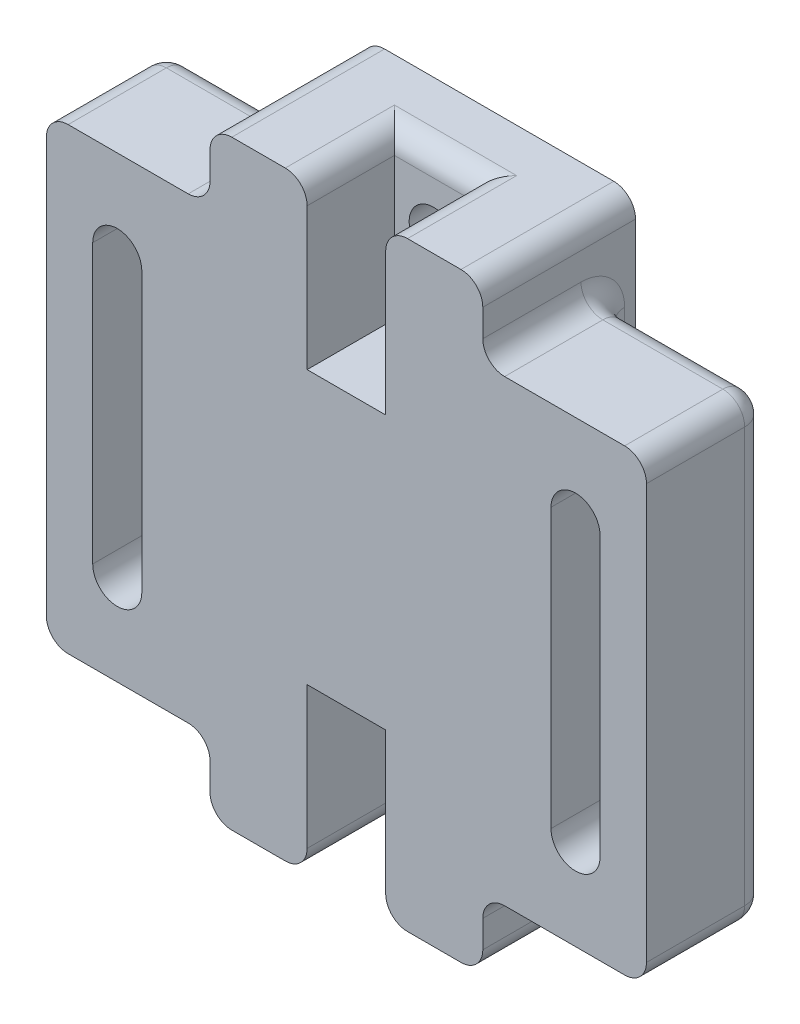
SolidWorks part; units mm, degrees
material "ABS"
ref_plane "Front Plane" through (0, 0, 0) normal (0, 0, 1) x (1, 0, 0)
ref_plane "Top Plane" through (0, 0, 0) normal (0, 1, 0) x (1, 0, 0)
ref_plane "Right Plane" through (0, 0, 0) normal (1, 0, 0) x (0, 0, -1)
sketch "Sketch1" plane through (0, 0, 0) normal (0, 1, 0) x (1, 0, 0)
  line L8 (0, 0) -> (15, 0)
  line L9 (15, 0) -> (15, 3)
  line L10 (15, 3) -> (40, 3)
  line L11 (40, 3) -> (40, 0)
  line L12 (40, 0) -> (55, 0)
  line L13 (55, 0) -> (55, -11)
  line L14 (55, -11) -> (0, -11)
  line L15 (0, -11) -> (0, 0)
  dimension "D1" = 55
  dimension "D2" = 14
  dimension "D3" = 11
  dimension "D4" = 25
extrude "Boss-Extrude1" add sketch "Sketch1" along normal blind 55
hole_wizard "M4 Clearance Hole1" positions "Sketch2" profile "Sketch3" hole size "M4" standard "ANSI Metric" end condition through all
sketch "Sketch2" plane through (0, 0, -3) normal (0, 0, -1) x (-1, 0, 0)
  line L0 (-27.5, 48.435) -> (-27.5, 6.565) construction
  line L4 (-40, 27.5) -> (-15, 27.5) construction
  line L5 (-40, 55) -> (-40, 0) construction
  line L6 (-15, 55) -> (-15, 0) construction
  point P0 (-27.5, 48.435)
  point P2 (-27.5, 6.565)
  point P27 (-27.5, 27.5)
  dimension "D1" = 41.87
sketch "Sketch3" plane through (27.5, 48.435, -3) normal (1, 0, 0) x (0, 1, 0)
  line L0 (0, 0) -> (0, 14)
  line L1 (0, 14) -> (2.25, 14)
  line L2 (2.25, 14) -> (2.25, 0)
  line L5 (2.25, 0) -> (0, 0)
  line L11 (0, -6.35) -> (0, 107.95) construction
  dimension "Thru Hole Dia." = 4.5
  dimension "Thru Hole Depth" = 14
hole_wizard "M4 Clearance Slot1" positions "Sketch4" profile "Sketch5" size "M4" standard "ANSI Metric" slot yes end condition through all
sketch "Sketch4" plane through (0, 0, 0) normal (0, 0, -1) x (-1, 0, 0)
  line L0 (-6.5, 42.5) -> (-6.5, 12.5) construction
  line L1 (0, 55) -> (0, 0) construction
  line L2 (-6.5, 27.5) -> (-48.5, 27.5) construction
  line L3 (-40, 55) -> (-15, 55) construction
  line L4 (-40, 55) -> (-15, 55) construction
  line L5 (-27.5, 55) -> (-27.5, 27.5) construction
  line L6 (-48.5, 27.5) -> (-55, 27.5) construction
  line L7 (-55, 55) -> (-55, 0) construction
  point P0 (-6.5, 27.5)
  point P4 (-48.5, 27.5)
  dimension "D1" = 30
  dimension "D3" = 42
sketch "Sketch5" plane through (6.5, 27.5, 0) normal (1, 0, 0) x (0, 1, 0)
  line L0 (0, 0) -> (0, 11)
  line L1 (0, 11) -> (2.25, 11)
  line L2 (2.25, 11) -> (2.25, 0)
  line L5 (2.25, 0) -> (0, 0)
  line L11 (0, -6.35) -> (0, 107.95) construction
  dimension "Thru Hole Dia." = 4.5
  dimension "Thru Hole Depth" = 11
sketch "Sketch6" plane through (0, 55, 0) normal (0, 1, 0) x (1, 0, 0)
  line L0 (0, -11) -> (55, -11) construction
  line L1 (23.9, -11) -> (31.1, -11)
  line L2 (23.9, -11) -> (23.9, -3)
  line L3 (23.9, -3) -> (31.1, -3)
  line L4 (31.1, -11) -> (31.1, -3)
  point P6 (27.5, -11)
  dimension "D1" = 7.2
  dimension "D2" = 8
extrude "Cut-Extrude1" cut sketch "Sketch6" against normal blind 15
ref_plane "Mirror Plane" through (0, 27.5, 0) normal (0, 1, 0) x (1, 0, 0)
mirror "Mirror1" about plane through (0, 27.5, 0) normal (0, 1, 0) of "Cut-Extrude1"
sketch "Sketch7" plane through (0, 0, 0) normal (0, 0, -1) x (-1, 0, 0)
  line L0 (-15, 0) -> (0, 0)
  line L1 (0, 0) -> (0, 6.5)
  line L2 (0, 55) -> (0, 0) construction
  line L3 (0, 6.5) -> (-15, 6.5)
  line L4 (-15, 55) -> (-15, 0) construction
  line L5 (-15, 0) -> (-15, 6.5)
  dimension "D1" = 6.5
extrude "Cut-Extrude3" cut sketch "Sketch7" against normal through all
ref_plane "Plane1" through (0, 27.5, 0) normal (0, -1, 0) x (-1, 0, 0)
ref_plane "Plane2" through (27.5, 0, 0) normal (1, 0, 0) x (0, 0, -1)
mirror "Mirror2" about plane through (0, 27.5, 0) normal (0, -1, 0) of "Cut-Extrude3"
mirror "Mirror3" about plane through (27.5, 0, 0) normal (1, 0, 0) of "Mirror2"
fillet "Fillet1" radius 2 26 edges at (40, 48.5, 5.5) (40, 6.5, 5.5) (47.5, 48.5, 0) (55, 27.5, 0) (47.5, 6.5, 0) (40, 27.5, 0) (15, 48.5, 5.5) (15, 27.5, 0) (55, 48.5, 5.5) (55, 6.5, 5.5) (0, 48.5, 5.5) (0, 6.5, 5.5) (7.5, 48.5, 0) (0, 27.5, 0) (7.5, 6.5, 0) (15, 6.5, 5.5) (23.9, 0, 7) (31.1, 0, 7) (27.5, 0, 3) (27.5, 55, 3) (23.9, 55, 7) (31.1, 55, 7) (40, 55, 4) (15, 55, 4) (15, 0, 4) (40, 0, 4)
